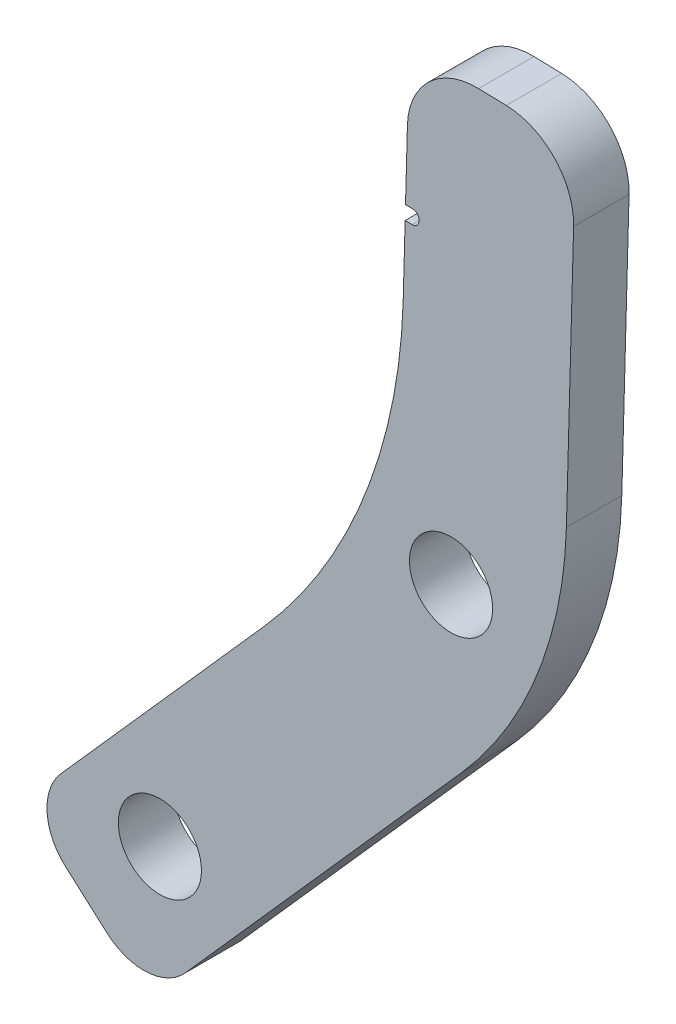
SolidWorks part; units mm, degrees
material "Acrylic (Medium-high impact)"
ref_plane "Front" through (0, 0, 0) normal (0, 0, 1) x (1, 0, 0)
ref_plane "Top" through (0, 0, 0) normal (0, 1, 0) x (1, 0, 0)
ref_plane "Right" through (0, 0, 0) normal (1, 0, 0) x (0, 0, -1)
sketch "Sketch1" plane through (0, 0, 0) normal (0, 0, 1) x (1, 0, 0)
  line L0 (7.9038, 3.731) -> (-21.9544, -29.9362)
  line L1 (8.862, 38.7179) -> (-3.1335, 39.0464)
  line L2 (-3.1335, 39.0464) -> (-3.9721, 8.4255)
  line L3 (-3.9721, 8.4255) -> (-30.9323, -21.974)
  line L4 (2.8642, 38.8822) -> (2.3284, 19.3174) construction
  line L5 (-21.9544, -29.9362) -> (-30.9323, -21.974)
  line L7 (7.9038, 3.731) -> (8.862, 38.7179)
  circle A0 centre (-21.1352, -19.9698) radius 3
  dimension "D3" = 6
  dimension "D4" = 8
  dimension "D5" = 12
  dimension "D7" = 90
  dimension "D2" = 12
  dimension "D9" = 35
  dimension "D10" = 140
extrude "Boss-Extrude1" add sketch "Sketch1" along normal blind 4
fillet "Fillet1" radius 4 2 edges at (-30.9323, -21.974, 2) (-21.9544, -29.9362, 2)
fillet "Fillet4" radius 30 1 edges at (7.9038, 3.731, 2)
fillet "Fillet5" radius 40 1 edges at (-3.9721, 8.4255, 2)
fillet "Fillet6" radius 5 2 edges at (8.862, 38.7179, 2) (-3.1335, 39.0464, 2)
sketch "Sketch6" plane through (0, 0, 4) normal (0, 0, 1) x (1, 0, 0)
  line L0 (6.1133, 4.4388) -> (-6.3594, 9.3692) construction
  arc A0 (0.6588, -4.4382) -> (8.2028, 14.6461) centre (-21.786, 15.4673) ccw construction
  arc A1 (-13.6321, -2.4668) -> (-3.5735, 22.9789) centre (-43.5586, 24.0739) ccw construction
  circle A2 centre (-0.1231, 6.904) radius 3
  dimension "D1" = 6
extrude "Cut-Extrude2" cut sketch "Sketch6" against normal blind 34
sketch "Sketch7" plane through (0, 0, 0) normal (0, 0, -1) x (-1, 0, 0)
  line L0 (3.2704, 34.0483) -> (3.5735, 22.9789) construction
  line L1 (2.422, 28.0136) -> (4.422, 28.0136)
  line L2 (2.422, 28.0136) -> (2.422, 29.0136)
  line L3 (2.422, 29.0136) -> (4.422, 29.0136)
  line L4 (4.422, 28.0136) -> (4.422, 29.0136)
  line L5 (2.422, 28.0136) -> (4.422, 29.0136) construction
  line L6 (2.422, 29.0136) -> (4.422, 28.0136) construction
  point P0 (3.422, 28.5136)
  dimension "D1" = 1
  dimension "D2" = 2
extrude "Cut-Extrude3" cut sketch "Sketch7" against normal blind 10
fillet "Fillet7" radius 0.5 2 edges at (-2.422, 29.0136, 2) (-2.422, 28.0136, 2)
